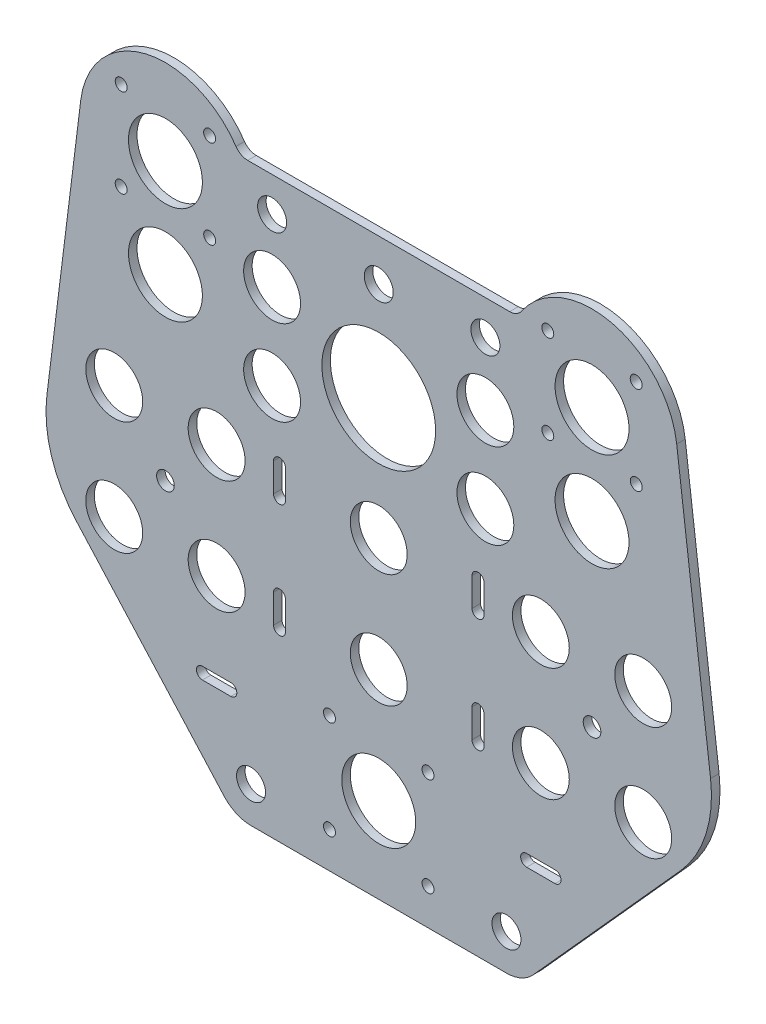
SolidWorks part; units mm, degrees
material "Thornel Mat VMA"
ref_plane "Front Plane" through (0, 0, 0) normal (0, 0, 1) x (1, 0, 0)
ref_plane "Top Plane" through (0, 0, 0) normal (0, 1, 0) x (1, 0, 0)
ref_plane "Right Plane" through (0, 0, 0) normal (1, 0, 0) x (0, 0, -1)
sketch "Model" plane through (0, 0, 0) normal (0, 0, 1) x (1, 0, 0)
  line L0 (-37, 2.8869) -> (-37, -7.1131)
  line L1 (-32.8, 2.8869) -> (-32.8, -7.1131)
  line L2 (-37, -37.1131) -> (-37, -47.1131)
  line L3 (-32.8, -37.1131) -> (-32.8, -47.1131)
  line L4 (-44.9, -112.1131) -> (0, -112.1131)
  line L5 (-46.0542, 89.8869) -> (0, 89.8869)
  line L6 (37, 2.8869) -> (37, -7.1131)
  line L7 (32.8, 2.8869) -> (32.8, -7.1131)
  line L8 (37, -37.1131) -> (37, -47.1131)
  line L9 (32.8, -37.1131) -> (32.8, -47.1131)
  line L10 (44.9, -112.1131) -> (0, -112.1131)
  line L11 (46.0542, 89.8869) -> (0, 89.8869)
  line L12 (-62, -72.1131) -> (-52, -72.1131)
  line L13 (-62, -76.3131) -> (-52, -76.3131)
  line L14 (62, -72.1131) -> (52, -72.1131)
  line L15 (62, -76.3131) -> (52, -76.3131)
  line L16 (-106.2292, -50.1976) -> (-54.3252, -107.9133)
  line L17 (106.2292, -50.1976) -> (54.3252, -107.9133)
  line L18 (-104.7711, 78.91) -> (-116.6795, -16.9345)
  line L19 (104.7711, 78.91) -> (116.6795, -16.9345)
  circle A0 centre (17.3241, -99.4372) radius 2.1
  circle A1 centre (-17.3241, -64.789) radius 2.1
  circle A2 centre (0, -82.1131) radius 13
  circle A3 centre (-75, 75.211) radius 13
  circle A4 centre (17.3241, -64.789) radius 2.1
  circle A5 centre (-17.3241, -99.4372) radius 2.1
  circle A6 centre (-75, -22.1131) radius 3.1
  circle A7 centre (-57, -2.1131) radius 10
  circle A8 centre (-57, -42.1131) radius 10
  arc A9 (-32.8, 2.8869) -> (-37, 2.8869) centre (-34.9, 2.8869) ccw
  arc A10 (-37, -7.1131) -> (-32.8, -7.1131) centre (-34.9, -7.1131) ccw
  arc A11 (-32.8, -37.1131) -> (-37, -37.1131) centre (-34.9, -37.1131) ccw
  arc A12 (-37, -47.1131) -> (-32.8, -47.1131) centre (-34.9, -47.1131) ccw
  circle A13 centre (-93, -2.1131) radius 10
  circle A14 centre (-93, -42.1131) radius 10
  circle A15 centre (-44.9, -99.4372) radius 5.1
  arc A16 (-50.1893, 92.0761) -> (-104.7711, 78.91) centre (-75, 75.211) ccw
  arc A17 (-50.1893, 92.0761) -> (-46.0542, 89.8869) centre (-46.0542, 94.8869) ccw
  circle A18 centre (75, -22.1131) radius 3.1
  circle A19 centre (57, -2.1131) radius 10
  circle A20 centre (57, -42.1131) radius 10
  arc A21 (37, 2.8869) -> (32.8, 2.8869) centre (34.9, 2.8869) ccw
  arc A22 (32.8, -7.1131) -> (37, -7.1131) centre (34.9, -7.1131) ccw
  arc A23 (37, -37.1131) -> (32.8, -37.1131) centre (34.9, -37.1131) ccw
  arc A24 (32.8, -47.1131) -> (37, -47.1131) centre (34.9, -47.1131) ccw
  circle A25 centre (93, -2.1131) radius 10
  circle A26 centre (93, -42.1131) radius 10
  circle A27 centre (44.9, -99.4372) radius 5.1
  arc A28 (-62, -72.1131) -> (-62, -76.3131) centre (-62, -74.2131) ccw
  arc A29 (-52, -76.3131) -> (-52, -72.1131) centre (-52, -74.2131) ccw
  arc A30 (62, -76.3131) -> (62, -72.1131) centre (62, -74.2131) ccw
  arc A31 (52, -72.1131) -> (52, -76.3131) centre (52, -74.2131) ccw
  circle A32 centre (0, 75.211) radius 5.1
  circle A33 centre (0, -2.1131) radius 10
  circle A34 centre (0, -42.1131) radius 10
  circle A35 centre (0, 40.5628) radius 20
  circle A36 centre (-37.5, 55.5628) radius 10
  circle A37 centre (-37.5, 25.5628) radius 10
  circle A38 centre (37.5, 55.5628) radius 10
  circle A39 centre (37.5, 25.5628) radius 10
  arc A40 (-54.3252, -107.9133) -> (-44.9, -112.1131) centre (-44.9, -99.4372) ccw
  arc A41 (44.9, -112.1131) -> (54.3252, -107.9133) centre (44.9, -99.4372) ccw
  circle A42 centre (75, 75.211) radius 13
  arc A43 (104.7711, 78.91) -> (50.1893, 92.0761) centre (75, 75.211) ccw
  arc A44 (46.0542, 89.8869) -> (50.1893, 92.0761) centre (46.0542, 94.8869) ccw
  arc A45 (-116.6795, -16.9345) -> (-106.2292, -50.1976) centre (-75, -22.1131) ccw
  arc A46 (106.2292, -50.1976) -> (116.6795, -16.9345) centre (75, -22.1131) ccw
  circle A47 centre (-75, 40.6882) radius 13
  circle A48 centre (75, 40.5628) radius 13
  circle A49 centre (-37.5, 77.7248) radius 5.1
  circle A50 centre (37.5, 77.7248) radius 5.1
  circle A51 centre (90.5324, 90.7434) radius 2.1
  circle A52 centre (59.4437, 90.7674) radius 2.1
  circle A53 centre (59.4437, 59.6547) radius 2.1
  circle A54 centre (90.5563, 59.6547) radius 2.1
  circle A55 centre (-59.4676, 90.7434) radius 2.1
  circle A56 centre (-90.5563, 90.7674) radius 2.1
  circle A57 centre (-90.5563, 59.6547) radius 2.1
  circle A58 centre (-59.4437, 59.6547) radius 2.1
extrude "Boss-Extrude1" add sketch "Model" along normal blind 3
